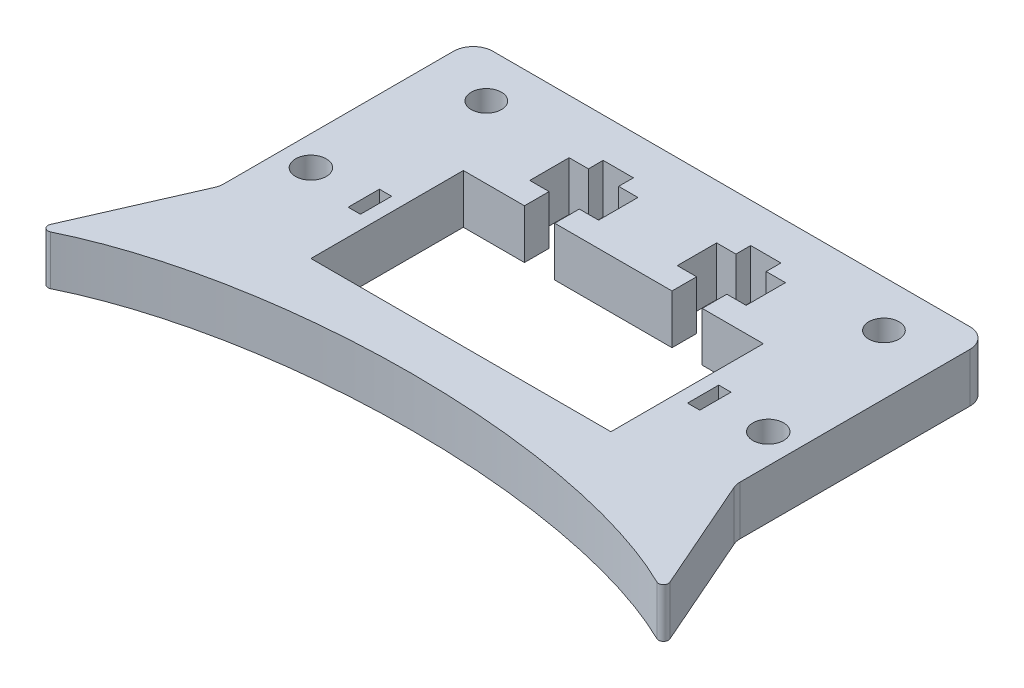
SolidWorks part; units mm, degrees
ref_plane "Front Plane" through (0, 0, 0) normal (0, 0, 1) x (1, 0, 0)
ref_plane "Top Plane" through (0, 0, 0) normal (0, 1, 0) x (1, 0, 0)
ref_plane "Right Plane" through (0, 0, 0) normal (1, 0, 0) x (0, 0, -1)
sketch "Sketch1" plane through (0, 0, 0) normal (0, 1, 0) x (1, 0, 0)
  line L1 (-52.5, -32.5) -> (52.5, -32.5)
  line L2 (-52.5, -32.5) -> (-52.5, 32.5)
  line L3 (-52.5, 32.5) -> (52.5, 32.5)
  line L4 (52.5, -32.5) -> (52.5, 32.5)
  line L5 (0, 32.5) -> (0, -32.5) construction
  line L6 (-52.5, 0) -> (52.5, 0) construction
  point P0 (0, 0)
  dimension "D1" = 105
  dimension "D2" = 65
extrude "Boss-Extrude1" add sketch "Sketch1" along normal blind 10
sketch "Sketch2" plane through (0, 10, 0) normal (0, 1, 0) x (1, 0, 0)
  line L6 (-30.5, 8.5) -> (30.5, 8.5)
  line L7 (-30.5, 8.5) -> (-30.5, -22.5)
  line L8 (-30.5, -22.5) -> (30.5, -22.5)
  line L9 (30.5, 8.5) -> (30.5, -22.5)
  line L10 (0, -22.5) -> (0, 8.5) construction
  line L11 (-30.5, -7) -> (30.5, -7) construction
  line L12 (0, 0) -> (0, -22.5) construction
  line L14 (-52.5, -32.5) -> (52.5, -32.5) construction
  point P0 (0, -7)
  dimension "D1" = 31
  dimension "D2" = 61
  dimension "D3" = 10
extrude "Cut-Extrude1" cut sketch "Sketch2" against normal through all
sketch "Sketch3" plane through (0, 10, 0) normal (0, 1, 0) x (1, 0, 0)
  line L0 (-15, 32.5) -> (-15, 9.5021) construction
  line L1 (52.5, 32.5) -> (-52.5, 32.5) construction
  line L3 (-22, 21.5) -> (-22, 13.5)
  line L4 (-18.075, 5.5043) -> (-11.925, 5.5043)
  line L5 (-18.075, 5.5043) -> (-18.075, 13.5)
  line L6 (-18.075, 13.5) -> (-11.925, 13.5)
  line L7 (-11.925, 5.5043) -> (-11.925, 13.5)
  line L8 (-15, 13.5) -> (-15, 5.5043) construction
  line L9 (-18.075, 9.5021) -> (-11.925, 9.5021) construction
  line L10 (-22, 21.5) -> (-8, 21.5)
  line L11 (-22, 13.5) -> (-8, 13.5)
  line L12 (-8, 21.5) -> (-8, 13.5)
  line L13 (-15, 13.5) -> (-15, 21.5) construction
  line L14 (-22, 17.5) -> (-8, 17.5) construction
  line L15 (0, 0) -> (0, 32.5) construction
  line L16 (-11.925, 18.5) -> (-18.075, 18.5)
  line L17 (-11.925, 18.5) -> (-11.925, 24.5)
  line L18 (-11.925, 24.5) -> (-18.075, 24.5)
  line L19 (-18.075, 18.5) -> (-18.075, 24.5)
  line L20 (-15, 24.5) -> (-15, 18.5) construction
  line L21 (-11.925, 21.5) -> (-18.075, 21.5) construction
  line L22 (30.5, 8.5) -> (-30.5, 8.5) construction
  point P10 (-15, 17.5)
  dimension "D1" = 6.15
  dimension "D2" = 5
  dimension "D3" = 14
  dimension "D4" = 8
  dimension "D5" = 16
  dimension "D6" = 15
extrude "Cut-Extrude2" cut sketch "Sketch3" against normal blind 10 contours L7 L6 L5 | L16 L19 L10 L3 L11 L6 L12 L17 | L19 L16 L17 L10 | L19 L10 L17 L18 region at (-15, 10, -17.0069) region at (-15, 10, -23) region at (-15, 10, -20) region at (-15, 10, -9.5021)
sketch "Sketch4" plane through (0, 10, 0) normal (0, 1, 0) x (1, 0, 0)
  line L2 (-46.5, -6.5) -> (-34.5, -6.5) construction
  line L3 (-18.075, 8.5) -> (-30.5, 8.5) construction
  line L4 (-33.25, -3.325) -> (-35.75, -3.325)
  line L5 (-33.25, -3.325) -> (-33.25, -9.675)
  line L6 (-33.25, -9.675) -> (-35.75, -9.675)
  line L7 (-35.75, -3.325) -> (-35.75, -9.675)
  line L8 (-34.5, -9.675) -> (-34.5, -3.325) construction
  line L9 (-33.25, -6.5) -> (-35.75, -6.5) construction
  line L10 (-30.5, 8.5) -> (-30.5, -22.5) construction
  circle A0 centre (-46.5, -6.5) radius 3.125
  dimension "D1" = 6.25
  dimension "D2" = 15
  dimension "D3" = 16
  dimension "D4" = 2.5
  dimension "D5" = 6.35
  dimension "D6" = 2.75
extrude "Cut-Extrude3" cut sketch "Sketch4" against normal through all
sketch "Sketch5" plane through (0, 0, 0) normal (0, 1, 0) x (1, 0, 0)
  line L0 (0, 0) -> (0, -65) construction
  line L1 (-52.5, -32.5) -> (52.5, -32.5) construction
  line L2 (-52.5, -19.0391) -> (-64.12, -45.5652)
  line L3 (-52.5, 32.5) -> (-52.5, -32.5) construction
  line L4 (-52.5, -19.0391) -> (0, -32.5)
  ellipse E0 centre (0, -65) end of major axis (-80, -65) minor radius 32.5
  dimension "D1" = 160
  dimension "D2" = 65
extrude "Boss-Extrude2" add sketch "Sketch5" along normal up to surface (10 mm away) contours E0 L4 L2 region at (-40.3234, 0, 30.8791) up to face at (-46.5, 10, 9.625)
sketch "Sketch6" plane through (0, 10, 0) normal (0, 1, 0) x (1, 0, 0)
  circle A0 centre (-40.4209, 23.095) radius 3.075
  dimension "D1" = 6.15
extrude "Cut-Extrude4" cut sketch "Sketch6" against normal through all
mirror "Mirror1" about plane through (0, 0, 0) normal (1, 0, 0) of "Cut-Extrude4", "Cut-Extrude3", "Cut-Extrude2", "Boss-Extrude2"
fillet "Fillet2" radius 1 2 edges at (-64.12, 5, 45.5652) (64.12, 5, 45.5652)
fillet "Fillet1" radius 4 4 edges at (-52.5, 5, 19.0391) (-52.5, 5, -32.5) (52.5, 5, 19.0391) (52.5, 5, -32.5)
